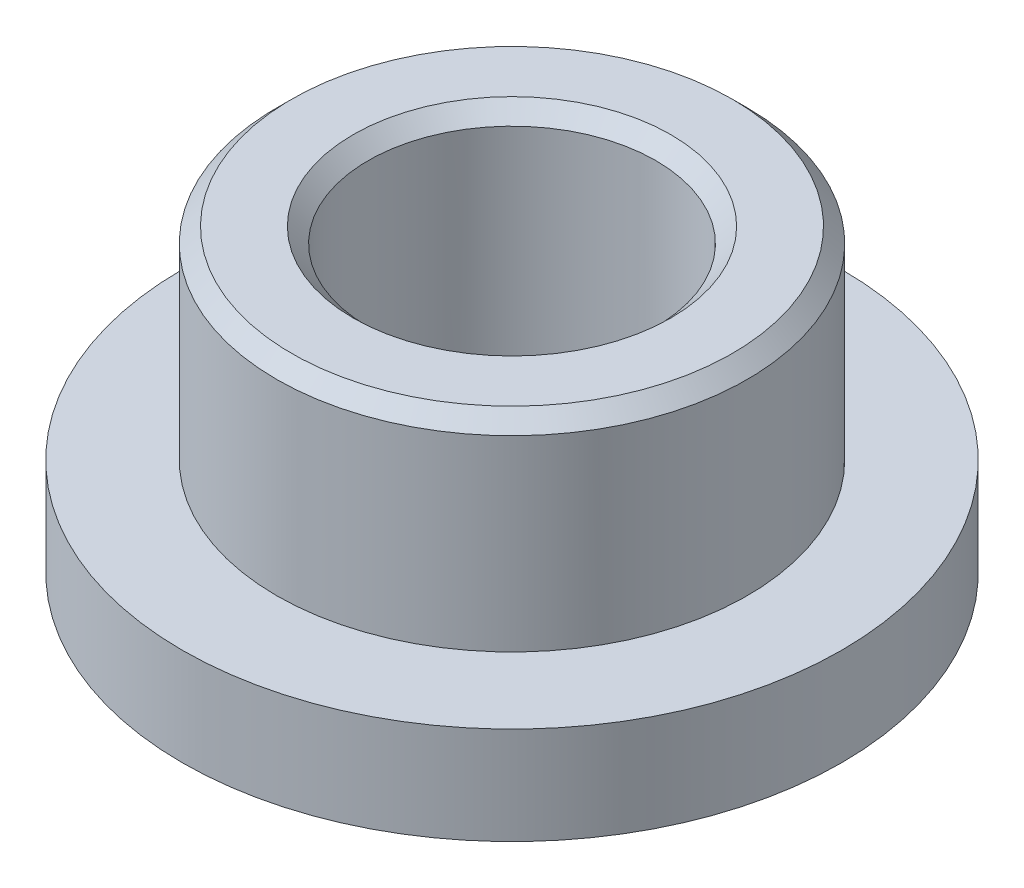
SolidWorks part; units mm, degrees
material "Brass"
ref_plane "Front" through (0, 0, 0) normal (0, 0, 1) x (1, 0, 0)
ref_plane "Top" through (0, 0, 0) normal (0, 1, 0) x (1, 0, 0)
ref_plane "Right" through (0, 0, 0) normal (1, 0, 0) x (0, 0, -1)
ref_axis "side-side" through (80.9, 0, 0) along (-1, 0, 0)
ref_axis "up-down" through (0, 50, 0) along (0, -1, 0)
ref_axis "front-back" through (0, 0, -80.9) along (0, 0, 1)
sketch "Sketch1" plane through (0, 0, 0) normal (0, 0, 1) x (1, 0, 0)
  line L3 (3.925, 1.6256) -> (3.925, 12.4)
  line L7 (5.5, 1.6256) -> (3.925, 1.6256)
  line L11 (5.5, 0) -> (5.5, 1.6256)
  line L15 (3.925, 12.4) -> (2.4, 12.4)
  line L18 (2.4, 0.2) -> (2.4, 12.4)
  line L22 (2.6, 0) -> (2.4, 0.2)
  line L27 (5.5, 0) -> (2.6, 0)
  line L28 (0, 0) -> (0, -3.6079) construction
  dimension "D1" = 1.6256
revolve "Revolve1" add sketch "Sketch1" angle 360 about L28
sketch "Sketch2" plane through (0, 0, 0) normal (0, 0, 1) x (1, 0, 0)
  line L0 (-5.5, 0) -> (5.5, 0) construction
  line L1 (-7, 13) -> (7, 13)
  line L2 (-7, 13) -> (-7, 5)
  line L3 (-7, 5) -> (7, 5)
  line L4 (7, 13) -> (7, 5)
  line L5 (0, 0) -> (0, 5) construction
  dimension "D1" = 5
  dimension "D2" = 14
  dimension "D3" = 8
extrude "Cut-Extrude1" cut sketch "Sketch2" against normal through all both and the other way through all
chamfer "Chamfer1" distance 0.25 angle 45 2 edges at (0, 5, -2.4) (0, 5, -3.925)
